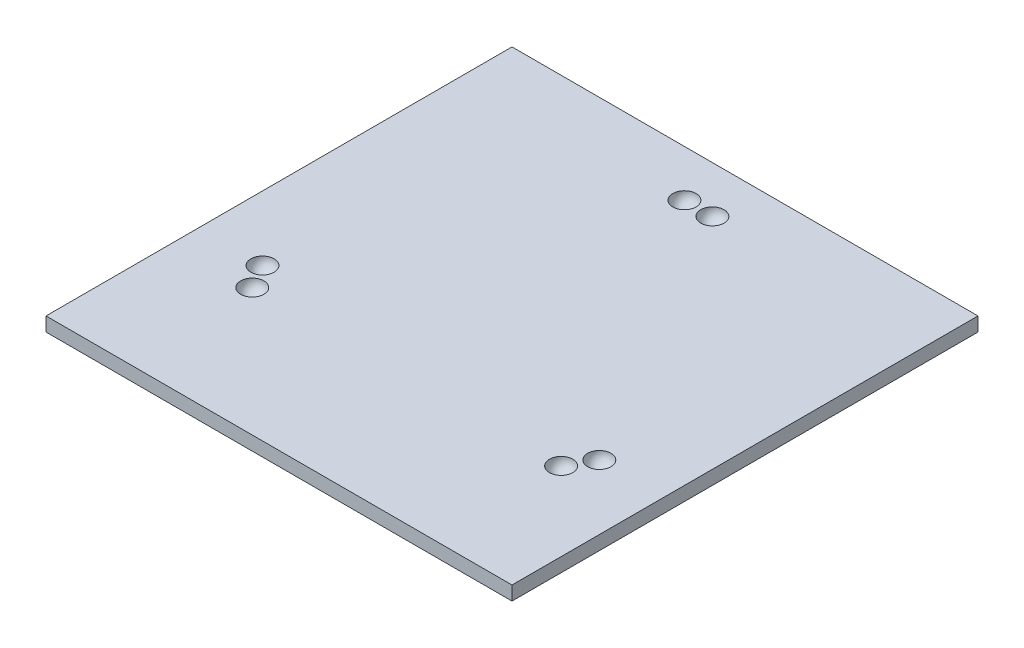
SolidWorks part; units mm, degrees
ref_plane "Front Plane" through (0, 0, 0) normal (0, 0, 1) x (1, 0, 0)
ref_plane "Top Plane" through (0, 0, 0) normal (0, 1, 0) x (1, 0, 0)
ref_plane "Right Plane" through (0, 0, 0) normal (1, 0, 0) x (0, 0, -1)
sketch "Sketch1" plane through (0, 0, 0) normal (0, 1, 0) x (1, 0, 0)
  line L1 (-100, -100) -> (100, -100)
  line L2 (-100, -100) -> (-100, 100)
  line L3 (-100, 100) -> (100, 100)
  line L4 (100, -100) -> (100, 100)
  line L5 (-100, -100) -> (100, 100) construction
  line L6 (-100, 100) -> (100, -100) construction
  point P0 (0, 0)
  dimension "D1" = 200
  dimension "D2" = 200
extrude "Boss-Extrude1" add sketch "Sketch1" along normal blind 6
ref_plane "Plane1" through (0, 0, -80) normal (0, 0, 1) x (1, 0, 0)
sketch "Sketch2" plane through (0, 0, -80) normal (0, 0, 1) x (1, 0, 0)
  line L0 (-11, 6) -> (-6, 6)
  line L1 (-6, 6) -> (-6, 1)
  line L3 (100, 6) -> (-100, 6) construction
  arc A0 (-6, 1) -> (-11, 6) centre (-6, 6) cw
  dimension "D1" = 5
  dimension "D2" = 6
revolve "Cut-Revolve1" cut sketch "Sketch2" angle 360 about L1
sketch "Sketch3" plane through (0, 6, 0) normal (0, 1, 0) x (1, 0, 0)
  point P0 (-69.282, -40)
  point P1 (0, 38.0133)
  dimension "D1" = 80
  dimension "D2" = 120
ref_plane "Plane2" through (0, 0, 40) normal (0, 0, 1) x (1, 0, 0)
ref_plane "Plane3" through (-69.282, 0, 0) normal (-1, 0, 0) x (0, 0, 1)
ref_axis "Axis1" through (-69.282, 6.3, 40) along (0, -1, 0)
ref_plane "Plane4" through (-69.282, 0, 40) normal (-0.866, 0, 0.5) x (0, -1, 0)
sketch "Sketch4" plane through (-69.282, 0, 40) normal (-0.866, 0, 0.5) x (0, -1, 0)
  line L0 (-1, 6) -> (-6, 6)
  line L1 (-6, 6) -> (-6, 11)
  line L2 (-6, -136.6025) -> (-6, 36.6025) construction
  arc A0 (-6, 11) -> (-1, 6) centre (-6, 6) cw
  dimension "D2" = 5
  dimension "D1" = 6
revolve "Cut-Revolve2" cut sketch "Sketch4" angle 360 about L0
ref_plane "Plane5" through (0, 0, 0) normal (-0.5, 0, -0.866) x (0, -1, 0)
mirror "Mirror1" about plane through (0, 0, 0) normal (-0.5, 0, -0.866) of "Cut-Revolve2"
mirror "Mirror2" about plane through (0, 0, 0) normal (1, 0, 0) of "Mirror1", "Cut-Revolve1"
